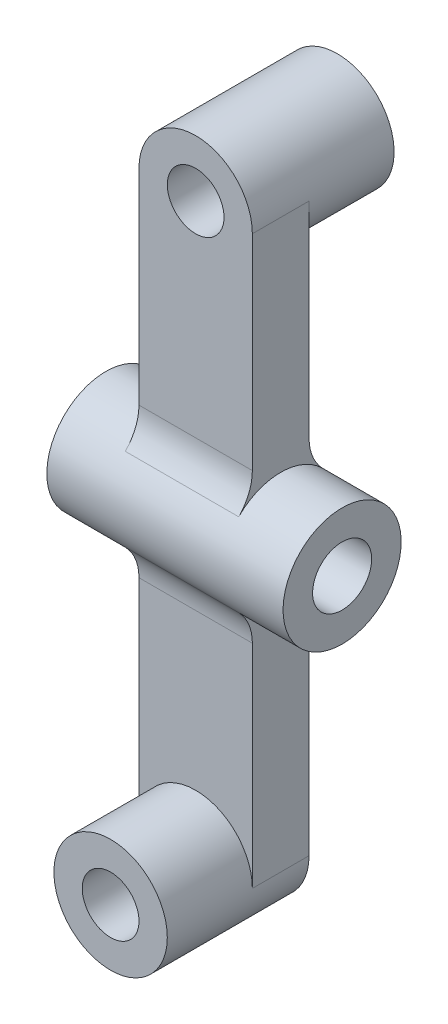
SolidWorks part; units mm, degrees
material "1060 Alloy"
ref_plane "Front Plane" through (0, 0, 0) normal (0, 0, 1) x (1, 0, 0)
ref_plane "Top Plane" through (0, 0, 0) normal (0, 1, 0) x (1, 0, 0)
ref_plane "Right Plane" through (0, 0, 0) normal (1, 0, 0) x (0, 0, -1)
sketch "Sketch2" plane through (0, 0, 0) normal (0, 0, 1) x (1, 0, 0)
  line L0 (0, 59.2258) -> (0, -60.7742) construction
  line L1 (12, 59.2258) -> (12, -60.7742)
  line L2 (-12, 59.2258) -> (-12, -60.7742)
  arc A0 (12, 59.2258) -> (-12, 59.2258) centre (0, 59.2258) ccw
  arc A1 (-12, -60.7742) -> (12, -60.7742) centre (0, -60.7742) ccw
  point P3 (0, -0.7742)
  dimension "D1" = 12
  dimension "D2" = 120
extrude "Boss-Extrude1" add sketch "Sketch2" along normal blind 12
ref_plane "Plane1" through (0, 0, 12) normal (0, 0, 1) x (1, 0, 0)
sketch "Sketch4" plane through (0, 0, 12) normal (0, 0, 1) x (1, 0, 0)
  line L2 (-12, 59.2258) -> (-12, -60.7742)
  line L3 (12, -60.7742) -> (12, 59.2258)
  circle A0 centre (0, 59.2258) radius 12
  circle A1 centre (0, -60.7742) radius 12
  arc A2 (12, 59.2258) -> (-12, 59.2258) centre (0, 59.2258) ccw
  arc A3 (-12, -60.7742) -> (12, -60.7742) centre (0, -60.7742) ccw
  arc A4 (12, 59.2258) -> (-12, 59.2258) centre (0, 59.2258) ccw
  arc A5 (-12, -60.7742) -> (12, -60.7742) centre (0, -60.7742) ccw
  arc M7 (-12, -60.7742) -> (12, -60.7742) centre (0, -60.7742) ccw
  dimension "D2" = 24
  dimension "D1" = 0
extrude "Boss-Extrude2" add sketch "Sketch4" along normal blind 18 contours A1 M7 region at (0, -60.7742, 12)
ref_plane "Plane2" through (0, 0, 0) normal (0, 0, -1) x (-1, 0, 0)
sketch "Sketch5" plane through (0, 0, 0) normal (0, 0, -1) x (-1, 0, 0)
  line L2 (-12, 59.2258) -> (-12, -60.7742)
  line L3 (12, -60.7742) -> (12, 59.2258)
  line L4 (-12, 59.2258) -> (-12, -60.7742)
  line L5 (12, -60.7742) -> (12, 59.2258)
  circle A0 centre (0, 59.2258) radius 12
  arc A2 (12, 59.2258) -> (-12, 59.2258) centre (0, 59.2258) ccw
  arc A3 (-12, -60.7742) -> (12, -60.7742) centre (0, -60.7742) ccw
  arc A4 (12, 59.2258) -> (-12, 59.2258) centre (0, 59.2258) ccw
  arc A5 (-12, -60.7742) -> (12, -60.7742) centre (0, -60.7742) ccw
  arc M6 (12, 59.2258) -> (-12, 59.2258) centre (0, 59.2258) ccw
  dimension "D2" = 24
  dimension "D1" = 0
extrude "Boss-Extrude3" add sketch "Sketch5" along normal blind 18 contours A0 M6 region at (0, 59.2258, 0)
ref_plane "Plane3" through (0, 0, 0) normal (-1, 0, 0) x (0, 0, 1)
sketch "Sketch8" plane through (-12, 0, 0) normal (-1, 0, 0) x (0, 0, 1)
  line L4 (0, 59.2258) -> (0, -60.7742)
  line L5 (0, -60.7742) -> (12, -60.7742)
  line L6 (12, -60.7742) -> (12, 59.2258)
  line L7 (12, 59.2258) -> (0, 59.2258)
  line L8 (0, 59.2258) -> (0, -60.7742)
  line L9 (0, -60.7742) -> (12, -60.7742)
  line L10 (12, -60.7742) -> (12, 59.2258)
  line L11 (12, 59.2258) -> (0, 59.2258)
  circle A0 centre (6, 0) radius 12.5
  point P2 (6, 59.2258)
  point P4 (12, -0.7742)
  dimension "D2" = 25
  dimension "D1" = 0
extrude "Boss-Extrude4" add sketch "Sketch8" along normal mid plane 50 from surface contours L10 A0 L8 | L8 A0 | L10 A0 region at (-12, 0, 6) region at (-12, 0, -2.6683) region at (-12, 0, 14.6683) starting at plane "Plane3"
sketch "Sketch9" plane through (-25, 0, 0) normal (-1, 0, 0) x (0, 0, 1)
  circle A0 centre (6, 0) radius 6.25
  circle A1 centre (6, 0) radius 12.5
  circle A2 centre (6, 0) radius 12.5
  dimension "D2" = 12.5
  dimension "D1" = 0
extrude "Cut-Extrude2" cut sketch "Sketch9" against normal through all contours A0
ref_plane "Plane5" through (-12, 10.9659, 0) normal (1, 0, 0) x (0, 0, -1)
fillet "Fillet1" radius 10 4 edges at (0, 10.9659, 12) (0, -10.9659, 12) (0, -10.9659, 0) (0, 10.9659, 0)
sketch "Sketch12" plane through (0, 0, -18) normal (0, 0, -1) x (-1, 0, 0)
  circle A0 centre (0, 59.2258) radius 6
  dimension "D2" = 12
extrude "Cut-Extrude3" cut sketch "Sketch12" against normal through all
sketch "Sketch13" plane through (0, 0, 30) normal (0, 0, 1) x (1, 0, 0)
  circle A0 centre (0, -60.7742) radius 6
  dimension "D2" = 12
extrude "Cut-Extrude6" cut sketch "Sketch13" against normal through all
equation "\"smallcircle\"=12"
equation "\"bigcircleextrude\"=24"
equation "\"D2@Sketch4\"=\"bigcircleextrude\""
equation "\"D2@Sketch12\"=\"smallcircle\""
